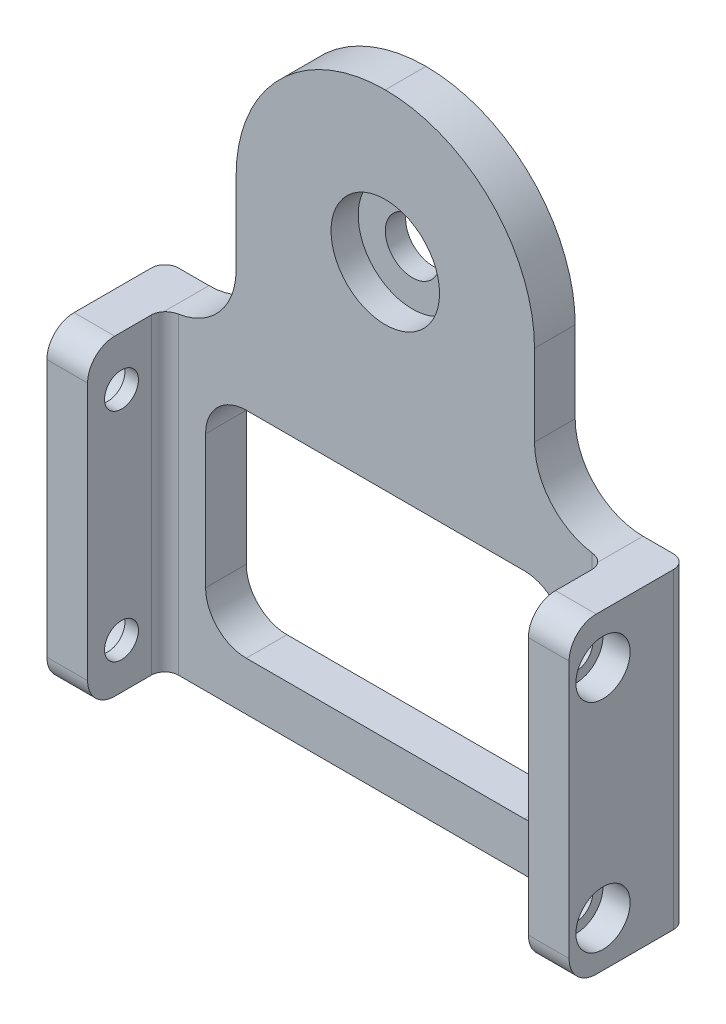
SolidWorks part; units mm, degrees
ref_plane "Front Plane" through (0, 0, 0) normal (0, 0, 1) x (1, 0, 0)
ref_plane "Top Plane" through (0, 0, 0) normal (0, 1, 0) x (1, 0, 0)
ref_plane "Right Plane" through (0, 0, 0) normal (1, 0, 0) x (0, 0, -1)
sketch "Sketch1" plane through (0, 0, 0) normal (0, 0, 1) x (1, 0, 0)
  line L0 (-11, 11.5) -> (-19.25, 11.5)
  line L1 (19.25, 11.5) -> (11, 11.5)
  line L2 (19.25, 11.5) -> (19.25, -11.5)
  line L3 (19.25, -11.5) -> (-19.25, -11.5)
  line L4 (-19.25, 11.5) -> (-19.25, -11.5)
  line L5 (19.25, 11.5) -> (-19.25, -11.5) construction
  line L6 (19.25, -11.5) -> (-19.25, 11.5) construction
  line L7 (-19.25, 11.5) -> (-16.25, 11.5)
  line L8 (-19.25, 11.5) -> (-19.25, -11.5)
  line L9 (-19.25, -11.5) -> (-16.25, -11.5)
  line L10 (-16.25, 11.5) -> (-16.25, -11.5)
  line L11 (19.25, 11.5) -> (16.25, 11.5)
  line L12 (19.25, 11.5) -> (19.25, -11.5)
  line L13 (19.25, -11.5) -> (16.25, -11.5)
  line L14 (16.25, 11.5) -> (16.25, -11.5)
  line L16 (-11, 11.5) -> (-11, 33.5)
  line L17 (-11, 33.5) -> (11, 33.5)
  line L18 (11, 11.5) -> (11, 33.5)
  line L20 (-13.25, 7.9156) -> (13.25, 7.9156)
  line L21 (-13.25, 7.9156) -> (-13.25, -7.9156)
  line L22 (-13.25, -7.9156) -> (13.25, -7.9156)
  line L23 (13.25, 7.9156) -> (13.25, -7.9156)
  line L24 (-13.25, 7.9156) -> (13.25, -7.9156) construction
  line L25 (-13.25, -7.9156) -> (13.25, 7.9156) construction
  circle A0 centre (0, 22.5) radius 2
  point P0 (0, 0)
  point P15 (0, 33.5)
  point P18 (0, 0)
  dimension "D10" = 4
  dimension "D1" = 32.5
  dimension "D2" = 3
  dimension "D3" = 3
  dimension "D4" = 22
  dimension "D5" = 23
  dimension "D6" = 11
  dimension "D7" = 0
  dimension "D8" = 6
extrude "Boss-Extrude1" add sketch "Sketch1" along normal blind 3 contours L1 L18 L17 L16 L0 L10 L3 L14 A0 region at (0, 13.2689, 0)
extrude "Boss-Extrude2" add sketch "Sketch1<4>" along normal blind 8.7 contours L1 L14 L3 L2 | L10 L0 L4 L3 region at (-17.75, 0, 0) region at (17.75, 0, 0)
sketch "Sketch1<4>" plane through (0, 0, 0) normal (0, 0, 1) x (1, 0, 0) same geometry as "Sketch1"
sketch "Sketch2" plane through (19.25, 0, 0) normal (1, 0, 0) x (0, 0, -1)
  line L0 (-8.7, 11.5) -> (0, 11.5) construction
  line L1 (-8.7, 11.5) -> (-8.7, -11.5) construction
  circle A0 centre (-6.2, 7.84) radius 1.25
  circle A1 centre (-6.2, -8.16) radius 1.25
  dimension "D1" = 2.5
  dimension "D2" = 3.66
  dimension "D3" = 2.5
  dimension "D4" = 16
extrude "Cut-Extrude1" cut sketch "Sketch2" against normal up to surface (38.5 mm away) up to face at (-19.25, 0, 4.35)
sketch "Sketch3" plane through (0, 0, 0) normal (0, 0, -1) x (-1, 0, 0)
  circle A0 centre (0, 22.5) radius 2.5
  circle A1 centre (0, 22.5) radius 2 construction
  circle M2 centre (0, 22.5) radius 2
  dimension "D1" = 0.5
extrude "Boss-Extrude4" add sketch "Sketch3" along normal blind 0.5 contours A0 M2 region at (2.4293, 22.5, 0)
fillet "Fillet1" radius 11 2 edges at (-11, 33.5, 1.5) (11, 33.5, 1.5)
fillet "Fillet2" radius 3 4 edges at (-13.25, 7.9156, 1.5) (-13.25, -7.9156, 1.5) (13.25, -7.9156, 1.5) (13.25, 7.9156, 1.5)
sketch "Sketch4" plane through (-19.25, 0, 0) normal (-1, 0, 0) x (0, 0, 1)
  circle A0 centre (6.2, 7.84) radius 2
  circle A1 centre (6.2, -8.16) radius 2
  dimension "D1" = 4
extrude "Cut-Extrude2" cut sketch "Sketch4" against normal blind 2
mirror "Mirror1" about plane through (0, 0, 0) normal (1, 0, 0) of "Cut-Extrude2"
fillet "Fillet3" radius 2 4 edges at (17.75, 11.5, 8.7) (17.75, -11.5, 8.7) (-17.75, -11.5, 8.7) (-17.75, 11.5, 8.7)
fillet "Fillet4" radius 1 4 edges at (19.25, 0, 0) (-19.25, 0, 0) (-16.25, 0, 3) (16.25, 0, 3)
fillet "Fillet5" radius 5 2 edges at (-11, 11.5, 1.5) (11, 11.5, 1.5)
sketch "Sketch5" plane through (0, 0, 3) normal (0, 0, 1) x (1, 0, 0)
  circle A0 centre (0, 22.5) radius 4
  dimension "D1" = 8
extrude "Cut-Extrude3" cut sketch "Sketch5" against normal offset from surface (2 mm away) 1 up to face at (2.5, 22.5, 0)
